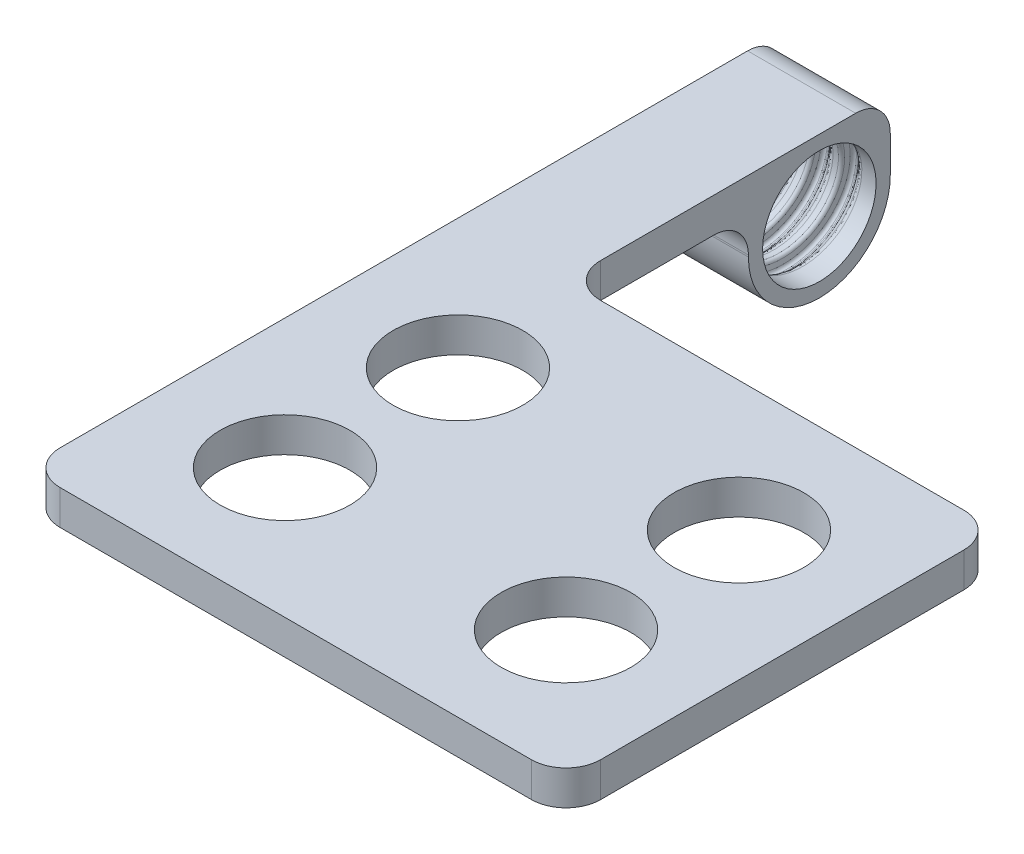
SolidWorks part; units mm, degrees
ref_plane "Alzado" through (0, 0, 0) normal (0, 0, 1) x (1, 0, 0)
ref_plane "Planta" through (0, 0, 0) normal (0, 1, 0) x (1, 0, 0)
ref_plane "Vista lateral" through (0, 0, 0) normal (1, 0, 0) x (0, 0, -1)
sketch "Croquis3" plane through (0, 0, 0) normal (0, 1, 0) x (1, 0, 0)
  line L1 (39.6875, 0) -> (39.6875, -31.75)
  line L2 (39.6875, -31.75) -> (0, -31.75)
  line L3 (0, -31.75) -> (0, 0)
  line L6 (7.9375, 23.8125) -> (0, 23.8125)
  line L8 (0, 13.3945) -> (0, 0)
  line L9 (0, 23.8125) -> (0, 13.3945)
  line L10 (0, 13.3945) -> (7.9375, 13.3945)
  line L11 (7.9375, 13.3945) -> (7.9375, 0)
  line L12 (7.9375, 0) -> (39.6875, 0)
  circle A0 centre (9.525, -9.525) radius 4.7625
  circle A1 centre (9.525, -22.225) radius 4.7625
  circle A2 centre (30.1625, -22.225) radius 4.7625
  circle A3 centre (30.1625, -9.525) radius 4.7625
sketch "Croquis5" plane through (0, 0, 0) normal (0, 1, 0) x (1, 0, 0)
  line L1 (0, 23.8125) -> (7.9375, 23.8125)
  line L2 (0, 23.8125) -> (0, 13.3945)
  line L3 (0, 13.3945) -> (7.9375, 13.3945)
  line L4 (7.9375, 23.8125) -> (7.9375, 13.3945)
extrude "Saliente-Extruir3" add sketch "Croquis5" against normal blind 10.418
fillet "Redondeo1" 2 edges at (3.9688, -10.418, -13.3945) (3.9688, -10.418, -23.8125) type full round first side face at (3.9688, -5.209, -13.3945) second side face at (3.9688, -5.209, -23.8125) middle face at (3.9688, -10.418, -18.6035)
extrude "Saliente-Extruir4" add sketch "Croquis3" against normal blind 2.54 contours L10 L11 L12 L1 L2 L3 L8
extrude "Cortar-Extruir2" cut sketch "Croquis3<9>" against normal blind 2.54 contours A0 | A3 | A2 | A1 region at (9.525, 0, 9.525) region at (9.525, 0, 22.225) region at (30.1625, 0, 22.225) region at (30.1625, 0, 9.525)
sketch "Croquis3<9>" plane through (0, 0, 0) normal (0, 1, 0) x (1, 0, 0) same geometry as "Croquis3"
fillet "Redondeo2" radius 2.54 1 edges at (3.9688, -2.54, -13.3945) type face fillet first side face at (9.525, -2.54, 26.9875) second side face at (3.9688, -3.8745, -13.3945)
sketch "Croquis6" plane through (7.9375, 0, 0) normal (1, 0, 0) x (0, 0, -1)
  circle A1 centre (18.6035, -5.209) radius 4.1672
extrude "Cortar-Extruir3" cut sketch "Croquis6" against normal through all
thread "Rosca1" pitch 2.1167 method cut profile "Perfil de rosca1" start angle 0, offset 0, length 0, pitch 2.1167, diameter 8.3344
ref_plane "Plano1" through (7.9375, -5.209, -14.4363) normal (0, -1, 0) x (0, 0, 1)
sketch "Perfil de rosca1" plane through (7.9375, -5.209, -14.4363) normal (0, -1, 0) x (0, 0, 1)
  line L0 (0, 0) -> (0, 2.1167) construction
  line L1 (0, 0) -> (0, 1.719)
  line L2 (0.254, 1.719) -> (0.762, 1.719) construction
  line L3 (0.762, 1.1583) -> (0.762, 1.0566)
  line L4 (0.5521, 1.4085) -> (0.2099, 1.4688)
  line L5 (0.7025, 0.9129) -> (0.1488, 0.3592)
  line L6 (0.508, 0) -> (0.762, 0) construction
  arc A0 (0.2099, 1.4688) -> (0, 1.719) centre (0.254, 1.719) cw
  arc A1 (0.1488, 0.3592) -> (0, 0) centre (0.508, 0) ccw
  arc A2 (0.762, 1.0566) -> (0.7025, 0.9129) centre (0.5588, 1.0566) cw
  arc A3 (0.762, 1.1583) -> (0.5521, 1.4085) centre (0.508, 1.1583) ccw
  point P10 (0.762, 1.3715)
  point P17 (0.762, 0.9724)
  point P18 (0, 1.5058)
  point P19 (0, 0.2104)
  point P20 (0, 0)
  dimension "RootFillet1" = 0.254
  dimension "RootFillet2" = 0.508
  dimension "CrestFillet2" = 0.2032
  dimension "CrestFillet1" = 0.254
  dimension "Pitch" = 2.1167
  dimension "Angle1" = 10
  dimension "Angle2" = 45
  dimension "a" = 1.2954
  dimension "b" = 0.762
  dimension "c" = 0.399
fillet "Redondeo4" radius 2.54 1 edges at (39.6875, -1.27, 0) type face fillet first side face at (23.8125, -1.27, 0) second side face at (39.6875, -1.27, 15.875)
fillet "Redondeo5" radius 2.54 1 edges at (39.6875, -1.27, 31.75) type face fillet first side face at (19.8438, -1.27, 31.75) second side face at (39.6875, -1.27, 17.145)
fillet "Redondeo6" radius 2.54 1 edges at (0, -1.27, 31.75) type face fillet first side face at (0, -3.6087, -3.1849) second side face at (18.5738, -1.27, 31.75)
fillet "Redondeo7" radius 2.54 1 edges at (3.9688, 0, -23.8125) type face fillet first side face at (3.9688, -2.6045, -23.8125) second side face at (9.525, 0, 26.9875)
fillet "Redondeo8" radius 2.54 1 edges at (7.9375, -1.27, 0) type face fillet first side face at (7.9375, -5.209, -14.4363) second side face at (22.5425, -1.27, 0)
ref_plane "Plano2" through (-7.62, 0, 0) normal (1, 0, 0) x (0, 0, -1)
